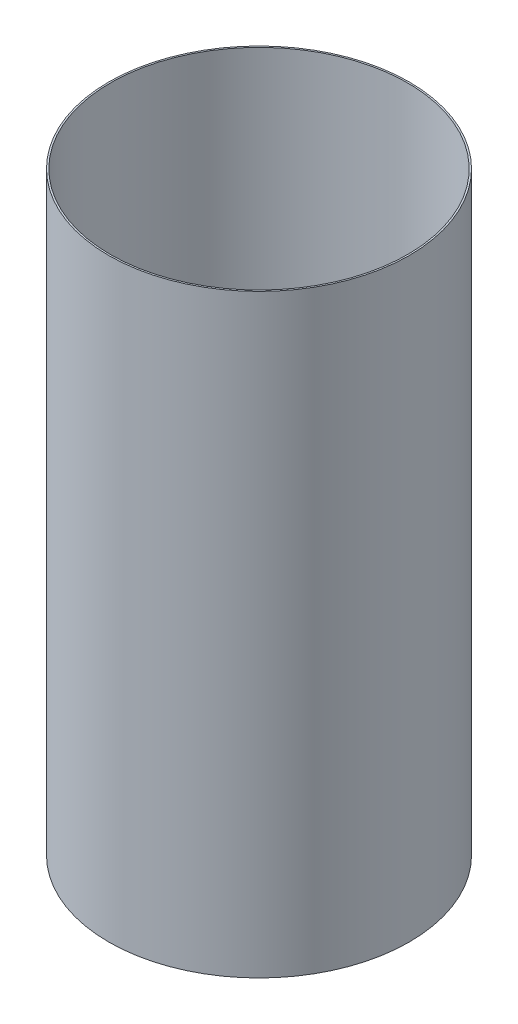
SolidWorks part; units mm, degrees
material "Glass"
ref_plane "Front Plane" through (0, 0, 0) normal (0, 0, 1) x (1, 0, 0)
ref_plane "Top Plane" through (0, 0, 0) normal (0, 1, 0) x (1, 0, 0)
ref_plane "Right Plane" through (0, 0, 0) normal (1, 0, 0) x (0, 0, -1)
sketch "Sketch1" plane through (0, 0, 0) normal (0, 1, 0) x (1, 0, 0)
  circle A0 centre (0, 0) radius 50.8
  dimension "D1" = 101.6
extrude "Extrude-Thin1" add sketch "Sketch1" along normal blind 203.2 thin thin type one direction wall 0.5588
